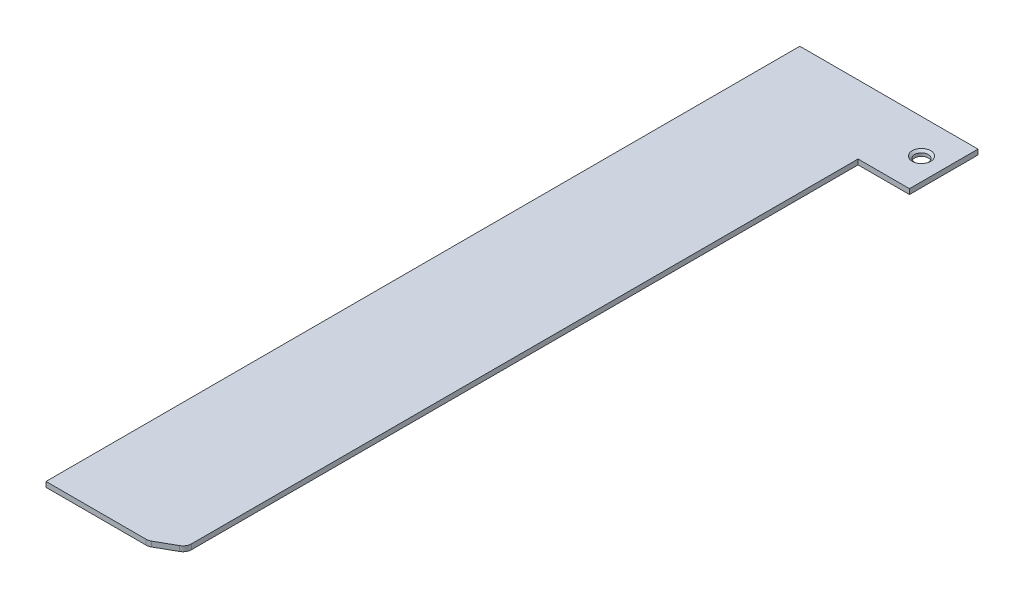
SolidWorks part; units mm, degrees
ref_plane "Front Plane" through (0, 0, 0) normal (0, 0, 1) x (1, 0, 0)
ref_plane "Top Plane" through (0, 0, 0) normal (0, 1, 0) x (1, 0, 0)
ref_plane "Right Plane" through (0, 0, 0) normal (1, 0, 0) x (0, 0, -1)
sketch "Sketch1" plane through (0, 0, 0) normal (0, 1, 0) x (1, 0, 0)
  line L0 (37, 220) -> (67, 220)
  line L1 (-37, 220) -> (37, 220)
  line L2 (-37, 220) -> (-37, -220)
  line L3 (-37, -220) -> (37, -220)
  line L4 (37, 180) -> (37, -220)
  line L5 (-37, 220) -> (37, -220) construction
  line L6 (-37, -220) -> (37, 220) construction
  line L7 (67, 220) -> (67, 180)
  line L8 (67, 180) -> (37, 180)
  point P0 (0, 0)
  dimension "D1" = 74
  dimension "D2" = 440
  dimension "D3" = 30
  dimension "D4" = 40
extrude "Boss-Extrude2" add sketch "Sketch1" along normal blind 3
hole_wizard "3/8-16 Tapped Hole1" positions "Sketch2" profile "Sketch3" tap size "3/8-16" standard "ANSI Inch" end condition through all
sketch "Sketch2" plane through (0, 3, 0) normal (0, 1, 0) x (1, 0, 0)
  line L0 (67, 180) -> (67, 220) construction
  line L2 (67, 220) -> (-37, 220) construction
  point P0 (54, 200)
  dimension "D1" = 13
  dimension "D2" = 20
sketch "Sketch3" plane through (54, 3, -200) normal (1, 0, 0) x (0, 0, 1)
  line L0 (0, 0) -> (0, 3)
  line L1 (0, 3) -> (3.9688, 3)
  line L2 (3.9688, 3) -> (3.9688, 1.1989)
  line L3 (3.9688, 1.1989) -> (5.3975, 0)
  line L5 (5.3975, 0) -> (0, 0)
  line L6 (-3.9688, 1.1989) -> (-5.3975, 0) construction
  line L11 (0, -6.35) -> (0, 107.95) construction
  dimension "Thread Major Dia." = 7.9375
  dimension "Thru Tap Drill Depth" = 3
  dimension "Near C'Sink Dia." = 10.795
  dimension "Near C'Sink Angle" = 100
sketch "Sketch4" plane through (0, 3, 0) normal (0, 1, 0) x (1, 0, 0)
  line L0 (0, -271.0672) -> (0, 271.0672) construction
  point P4 (0, 0)
ref_axis "Axis1" through (0, 3, 271.0672) along (0, 0, -1)
sketch "Sketch5" plane through (0, 0, 0) normal (0, -1, 0) x (1, 0, 0)
  line L0 (37, 220) -> (37, 211.9608)
  line L1 (37, 220) -> (37, -180) construction
  line L2 (-10.6202, 238.9098) -> (501.61, -50.9693) construction
  line L3 (37, 211.9608) -> (22.7944, 220)
  line L4 (-37, 220) -> (37, 220) construction
  line L5 (22.7944, 220) -> (37, 220)
extrude "Cut-Extrude1" cut sketch "Sketch5" against normal blind 10
fillet "Fillet1" radius 5 1 edges at (37, 1.5, 211.9608) type face fillet first side face at (29.8972, 1.5, 215.9804) second side face at (37, 1.5, 15.9804)
fillet "Fillet2" radius 5 1 edges at (22.7944, 1.5, 220) type face fillet first side face at (28.6285, 1.5, 216.6984) second side face at (-7.1028, 1.5, 220)
